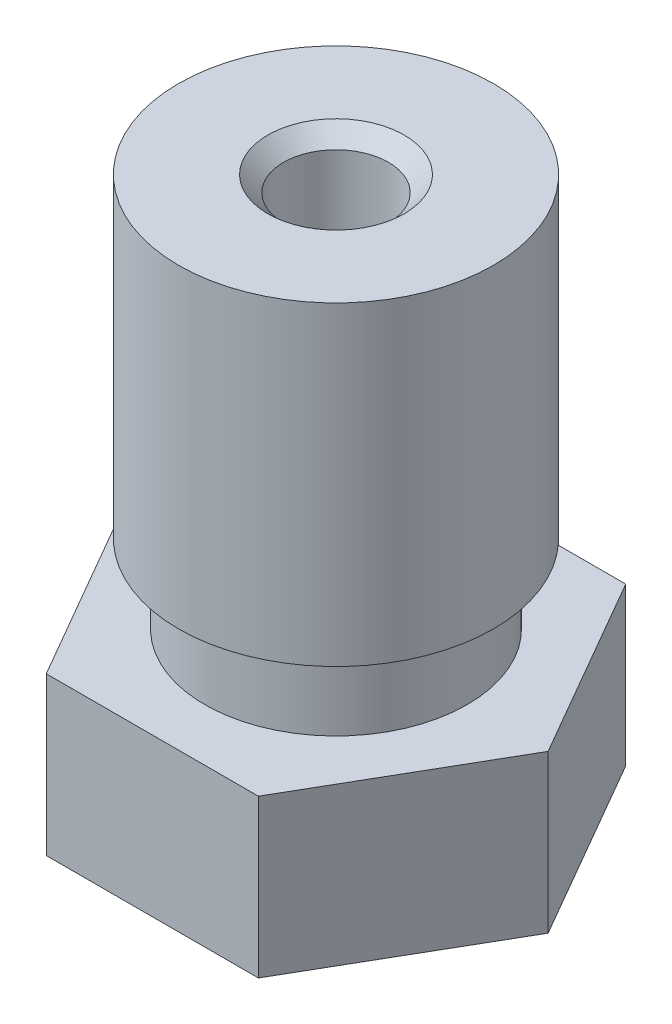
SolidWorks part; units mm, degrees
material "Brass"
ref_plane "Front Plane" through (0, 0, 0) normal (0, 0, 1) x (1, 0, 0)
ref_plane "Top Plane" through (0, 0, 0) normal (0, 1, 0) x (1, 0, 0)
ref_plane "Right Plane" through (0, 0, 0) normal (1, 0, 0) x (0, 0, -1)
sketch "Sketch1" plane through (0, 0, 0) normal (0, 0, 1) x (1, 0, 0)
  line L0 (0, 0) -> (0.5, 0)
  line L1 (0.5, 0) -> (1.9004, 2)
  line L2 (1.9004, 2) -> (3.5, 2)
  line L3 (3.5, 2) -> (3.5, 5)
  line L4 (3.5, 5) -> (2.5, 5)
  line L5 (2.5, 5) -> (2.5, 6.5)
  line L6 (2.5, 6.5) -> (3, 6.5)
  line L7 (3, 6.5) -> (3, 12.5)
  line L8 (3, 12.5) -> (0, 12.5)
  line L9 (0, 12.5) -> (0, 0)
  line L11 (0, -1.1291) -> (0, -50001.1291) construction
  dimension "D1" = 125
  dimension "D2" = 1
  dimension "D3" = 7
  dimension "D4" = 5
  dimension "D5" = 6
  dimension "D6" = 6
  dimension "D7" = 7.5
  dimension "D8" = 10.5
  dimension "D9" = 12.5
revolve "Revolve1" add sketch "Sketch1" angle 360 about L11
sketch "Sketch2" plane through (0, 0, 0) normal (0, 0, 1) x (1, 0, 0)
  line L0 (0, 0) -> (0, 12.5) construction
  line L1 (3, 12.5) -> (-3, 12.5) construction
  line L2 (0, 12.5) -> (1.3, 12.5)
  line L3 (1, 12.2) -> (1, 1.9856)
  line L4 (1, 1.9856) -> (0.2, 0.6)
  line L5 (0.2, 0.6) -> (0.2, 0)
  line L6 (-0.5, 0) -> (0.5, 0) construction
  line L7 (0.2, 0) -> (0, 0)
  line L8 (0, 0) -> (0, 12.5)
  line L9 (1, 12.2) -> (1.3, 12.5)
  dimension "D1" = 0.4
  dimension "D2" = 2
  dimension "D3" = 1.3
  dimension "D4" = 30
  dimension "D5" = 0.6
  dimension "D6" = 45
revolve "Cut-Revolve1" cut sketch "Sketch2" angle 360 about L0
sketch "Sketch3" plane through (0, 2, 0) normal (0, -1, 0) x (1, 0, 0)
  line L1 (4.0415, 0) -> (2.0207, 3.5)
  line L2 (2.0207, 3.5) -> (-2.0207, 3.5)
  line L3 (-2.0207, 3.5) -> (-4.0415, 0)
  line L4 (-4.0415, 0) -> (-2.0207, -3.5)
  line L5 (-2.0207, -3.5) -> (2.0207, -3.5)
  line L6 (2.0207, -3.5) -> (4.0415, 0)
  circle A0 centre (0, 0) radius 3.5 construction
  circle A1 centre (0, 0) radius 3.5
  circle A2 centre (0, 0) radius 3.5
  circle M3 centre (0, 0) radius 3.5
  dimension "D1" = 0
extrude "Boss-Extrude1" add sketch "Sketch3" against normal blind 3 contours L3 L4 M3 | L2 L3 M3 | L1 L2 M3 | L5 L6 M3 | L4 L5 M3 | L6 L1 M3 region at (3.6175, 2, 0) region at (1.8087, 2, 3.1328) region at (1.8087, 2, -3.1328) region at (-1.8087, 2, 3.1328) region at (-1.8087, 2, -3.1328) region at (-3.6175, 2, 0)
